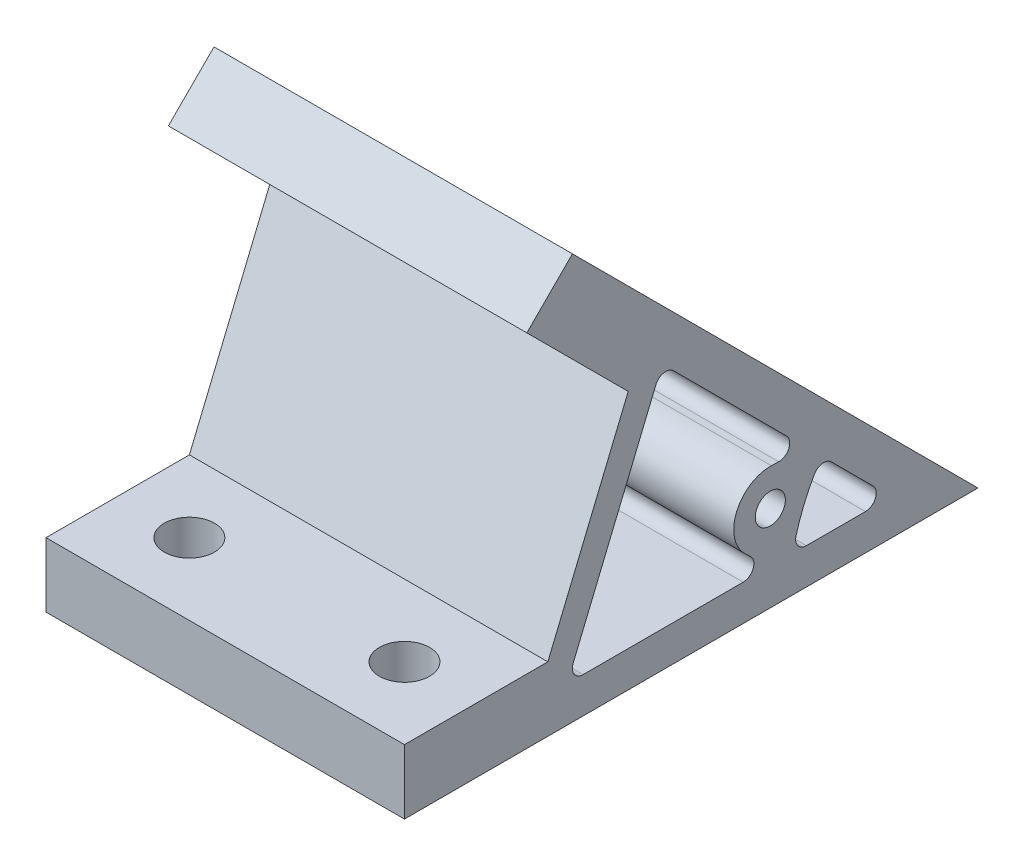
SolidWorks part; units mm, degrees
ref_plane "Front Plane" through (0, 0, 0) normal (0, 0, 1) x (1, 0, 0)
ref_plane "Top Plane" through (0, 0, 0) normal (0, 1, 0) x (1, 0, 0)
ref_plane "Right Plane" through (0, 0, 0) normal (1, 0, 0) x (0, 0, -1)
ref_plane "Plane1" through (0, 0, 0) normal (1, 0, 0) x (0, 0, -1)
sketch "Sketch1" plane through (0, 0, 0) normal (1, 0, 0) x (0, 0, -1)
  line L0 (-80, 0) -> (0, 0)
  line L1 (0, 0) -> (-56.5685, 56.5685)
  line L2 (-56.5685, 56.5685) -> (-62.9325, 50.2046)
  line L3 (-62.9325, 50.2046) -> (-48.7904, 36.0624)
  line L4 (-48.7904, 36.0624) -> (-60, 9)
  line L5 (-60, 9) -> (-80, 9)
  line L6 (-80, 9) -> (-80, 0)
  line L7 (-23.933, 5) -> (-15.6924, 5)
  line L8 (-14.6317, 7.5607) -> (-20.4587, 13.3877)
  line L9 (-55.0824, 5) -> (-32.7559, 5)
  line L10 (-31.7285, 7.5929) -> (-32.4639, 8.2843)
  line L11 (-28.8133, 17.0976) -> (-27.8044, 17.0665)
  line L12 (-26.6975, 19.6264) -> (-42.4847, 35.4136)
  line L13 (-44.9311, 34.927) -> (-56.4682, 7.074)
  arc A0 (-25.3806, 6.8931) -> (-23.933, 5) centre (-23.933, 6.5) ccw
  arc A1 (-15.6924, 5) -> (-14.6317, 7.5607) centre (-15.6924, 6.5) ccw
  arc A2 (-20.4587, 13.3877) -> (-22.821, 13.0726) centre (-21.5194, 12.327) ccw
  arc A3 (-22.821, 13.0726) -> (-25.3806, 6.8931) centre (0, 0) ccw
  circle A4 centre (-28.9706, 12) radius 2.1
  arc A5 (-56.4682, 7.074) -> (-55.0824, 5) centre (-55.0824, 6.5) ccw
  arc A6 (-32.7559, 5) -> (-31.7285, 7.5929) centre (-32.7559, 6.5) ccw
  arc A7 (-32.4639, 8.2843) -> (-28.8133, 17.0976) centre (-28.9706, 12) cw
  arc A8 (-27.8044, 17.0665) -> (-26.6975, 19.6264) centre (-27.7581, 18.5657) ccw
  arc A9 (-42.4847, 35.4136) -> (-44.9311, 34.927) centre (-43.5453, 34.3529) ccw
extrude "Boss-Extrude1" add sketch "Sketch1" against normal blind 25 and the other way blind 25
ref_plane "Plane2" through (0, -6.364, 6.364) normal (0, -0.7071, 0.7071) x (1, 0, 0)
sketch "Sketch2" plane through (0, -6.364, 6.364) normal (0, -0.7071, 0.7071) x (1, 0, 0)
  circle A0 centre (-15, 70) radius 3.5
extrude "Cut-Extrude1" cut sketch "Sketch2" against normal blind 9
ref_plane "Plane3" through (0, -6.364, 6.364) normal (0, -0.7071, 0.7071) x (1, 0, 0)
sketch "Sketch3" plane through (0, -6.364, 6.364) normal (0, -0.7071, 0.7071) x (1, 0, 0)
  circle A0 centre (15, 70) radius 3.5
extrude "Cut-Extrude2" cut sketch "Sketch3" against normal blind 9
ref_plane "Plane4" through (0, 0, 0) normal (0, 1, 0) x (1, 0, 0)
sketch "Sketch4" plane through (0, 0, 0) normal (0, 1, 0) x (1, 0, 0)
  circle A0 centre (-15, -70) radius 3.5
extrude "Cut-Extrude3" cut sketch "Sketch4" along normal blind 9
ref_plane "Plane5" through (0, 0, 0) normal (0, 1, 0) x (1, 0, 0)
sketch "Sketch5" plane through (0, 0, 0) normal (0, 1, 0) x (1, 0, 0)
  circle A0 centre (15, -70) radius 3.5
extrude "Cut-Extrude4" cut sketch "Sketch5" along normal blind 9
